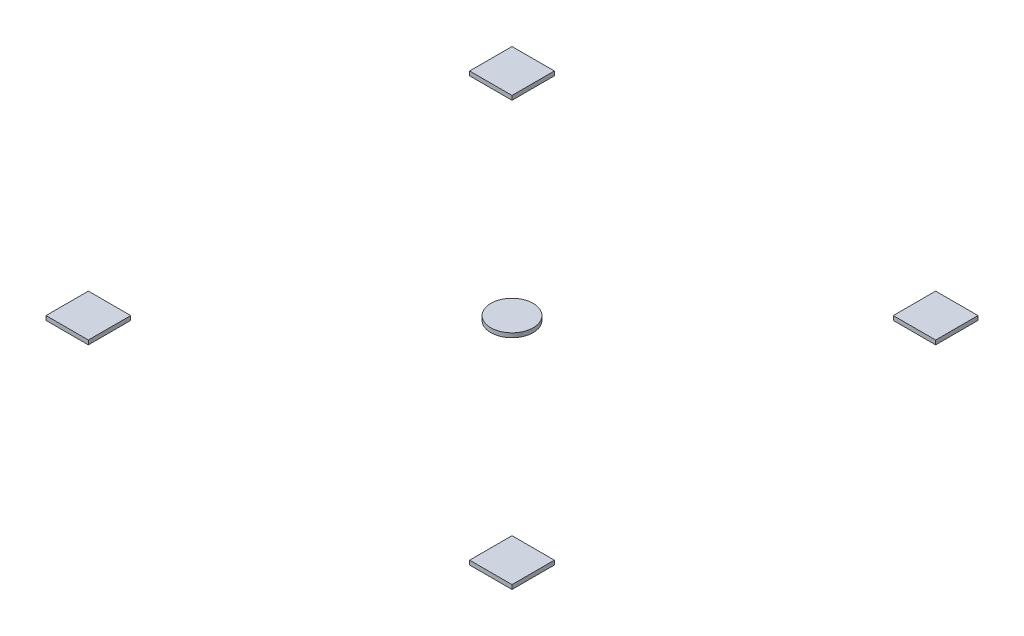
SolidWorks part; units mm, degrees
ref_plane "Ebene vorne" through (0, 0, 0) normal (0, 0, 1) x (1, 0, 0)
ref_plane "Ebene oben" through (0, 0, 0) normal (0, 1, 0) x (1, 0, 0)
ref_plane "Ebene rechts" through (0, 0, 0) normal (1, 0, 0) x (0, 0, -1)
sketch "Skizze1" plane through (0, 0, 0) normal (0, 1, 0) x (1, 0, 0)
  line L0 (0, 0) -> (0, 100) construction
  line L1 (0, 100) -> (-100, 100) construction
  line L2 (-100, 100) -> (0, 0) construction
  line L3 (110, 90) -> (110, 110)
  line L4 (-90, 110) -> (-110, 110)
  line L5 (-90, 110) -> (-90, 90)
  line L6 (-90, 90) -> (-110, 90)
  line L7 (-110, 110) -> (-110, 90)
  line L8 (-90, 110) -> (-110, 90) construction
  line L9 (-90, 90) -> (-110, 110) construction
  line L10 (110, 90) -> (90, 90)
  line L11 (90, 90) -> (90, 110)
  line L12 (110, 110) -> (90, 110)
  line L13 (100, 0) -> (100, 100) construction
  line L14 (0, 0) -> (100, 0) construction
  line L15 (110, 90) -> (90, 110) construction
  line L16 (100, 100) -> (0, 0) construction
  line L17 (90, 90) -> (110, 110) construction
  line L18 (90, -110) -> (110, -110)
  line L19 (90, -110) -> (90, -90)
  line L20 (90, -90) -> (110, -90)
  line L21 (110, -110) -> (110, -90)
  line L22 (0, -100) -> (100, -100) construction
  line L23 (0, 0) -> (0, -100) construction
  line L24 (90, -110) -> (110, -90) construction
  line L25 (100, -100) -> (0, 0) construction
  line L26 (90, -90) -> (110, -110) construction
  line L27 (-110, -90) -> (-110, -110)
  line L28 (-110, -90) -> (-90, -90)
  line L29 (-90, -90) -> (-90, -110)
  line L30 (-110, -110) -> (-90, -110)
  line L31 (-100, 0) -> (-100, -100) construction
  line L32 (0, 0) -> (-100, 0) construction
  line L33 (-110, -90) -> (-90, -110) construction
  line L34 (-100, -100) -> (0, 0) construction
  line L35 (-90, -90) -> (-110, -110) construction
  circle A0 centre (0, 0) radius 10
  point P29 (0, 0)
  dimension "D4" = 20
  dimension "D1" = 20
  dimension "D3" = 200
  dimension "D2" = 4
extrude "Aufsatz-Linear austragen1" add sketch "Skizze1" along normal blind 2
